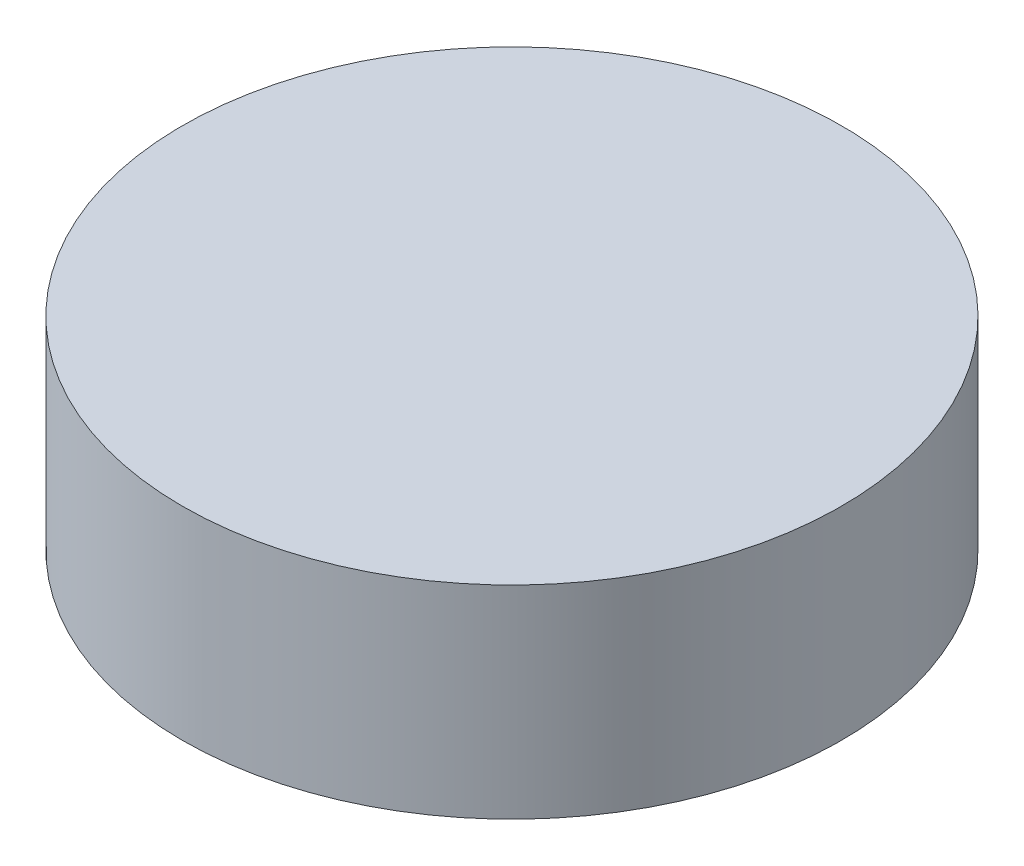
SolidWorks part; units mm, degrees
ref_plane "Front Plane" through (0, 0, 0) normal (0, 0, 1) x (1, 0, 0)
ref_plane "Top Plane" through (0, 0, 0) normal (0, 1, 0) x (1, 0, 0)
ref_plane "Right Plane" through (0, 0, 0) normal (1, 0, 0) x (0, 0, -1)
sketch "Sketch1" plane through (0, 0, 0) normal (0, 1, 0) x (1, 0, 0)
  circle A0 centre (0, 0) radius 32.5
  dimension "D1" = 65
extrude "Boss-Extrude1" add sketch "Sketch1" along normal mid plane 20
sketch "Sketch2" plane through (0, -10, 0) normal (0, -1, 0) x (1, 0, 0)
  circle A0 centre (0, 0) radius 21.5
  circle A1 centre (0, 0) radius 32.5 construction
  dimension "D1" = 11
extrude "Cut-Extrude1" cut sketch "Sketch2" against normal blind 15
